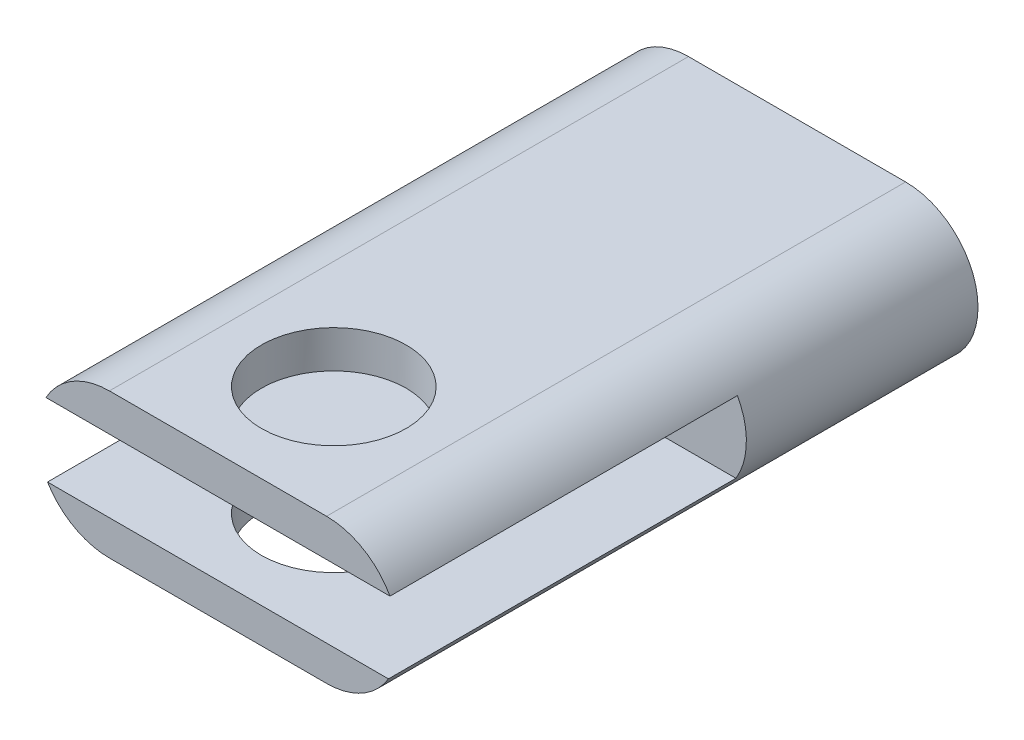
SolidWorks part; units mm, degrees
ref_plane "Front Plane" through (0, 0, 0) normal (0, 0, 1) x (1, 0, 0)
ref_plane "Top Plane" through (0, 0, 0) normal (0, 1, 0) x (1, 0, 0)
ref_plane "Right Plane" through (0, 0, 0) normal (1, 0, 0) x (0, 0, -1)
sketch "Sketch1" plane through (0, 0, 0) normal (0, 0, 1) x (1, 0, 0)
  line L0 (-375, 0) -> (375, 0) construction
  line L1 (-375, 250) -> (375, 250)
  line L2 (-375, -250) -> (375, -250)
  arc A0 (-375, 250) -> (-375, -250) centre (-375, 0) ccw
  arc A1 (375, -250) -> (375, 250) centre (375, 0) ccw
  point P3 (0, 0)
  point P8 (0, 0)
  dimension "D2" = 250
  dimension "D1" = 750
extrude "Boss-Extrude1" add sketch "Sketch1" along normal blind 2000
sketch "Sketch2" plane through (0, 0, 2000) normal (0, 0, 1) x (1, 0, 0)
  line L0 (-625, 0) -> (625, 0) construction
  line L1 (-625, -129.4673) -> (-625, 120.5327)
  line L2 (-625, 120.5327) -> (625, 120.5327)
  line L3 (625, 120.5327) -> (625, -129.4673)
  line L4 (625, -129.4673) -> (-625, -129.4673)
  arc A0 (375, -250) -> (375, 250) centre (375, 0) ccw construction
  point P6 (0, 0)
  point P10 (-625, -4.4673)
  dimension "D1" = 250
extrude "Cut-Extrude1" cut sketch "Sketch2" against normal blind 1200 contours L2 L3 L4 L1
sketch "Sketch3" plane through (0, 250, 0) normal (0, 1, 0) x (1, 0, 0)
  line L0 (0, -2000) -> (0, -1600) construction
  line L1 (375, -2000) -> (-375, -2000) construction
  circle A0 centre (0, -1600) radius 250
  dimension "D1" = 500
  dimension "D2" = 400
extrude "Cut-Extrude2" cut sketch "Sketch3" against normal through all contours A0
